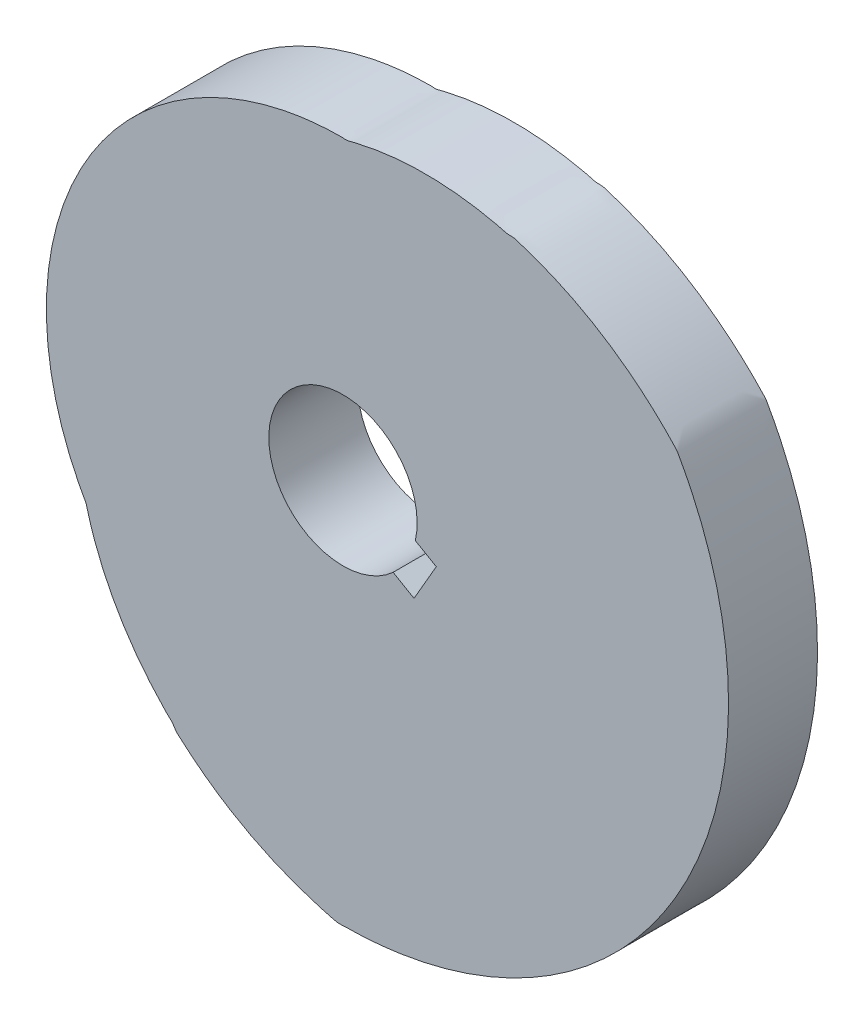
SolidWorks part; units mm, degrees
material "45"
ref_plane "前视基准面" through (0, 0, 0) normal (0, 0, 1) x (1, 0, 0)
ref_plane "上视基准面" through (0, 0, 0) normal (0, 1, 0) x (1, 0, 0)
ref_plane "右视基准面" through (0, 0, 0) normal (1, 0, 0) x (0, 0, -1)
ref_axis "基准轴1" through (0, 0, -88.99) along (0, 0, 1)
sketch "草图1" plane through (0, 0, 0) normal (0, 0, 1) x (1, 0, 0)
  arc A0 (45.0333, 26) -> (0, -52) centre (0, 0) cw construction
  arc A1 (-34.641, -20) -> (0, 40) centre (0, 0) cw construction
  spline S0 degree 3 poles (0, 40) (0.4897, 39.8817) (1.1754, 40.1373) (2.1153, 40.3446) (2.8327, 40.5043) (3.5567, 40.647) (4.2864, 40.7779) (5.0218, 40.8954) (5.7626, 40.9996) (6.5085, 41.0903) (7.2594, 41.1674) (8.0149, 41.2308) (8.7749, 41.2803) (9.539, 41.3157) (10.307, 41.337) (11.0786, 41.344) (11.8536, 41.3366) (12.6317, 41.3147) (13.4126, 41.2782) (14.1961, 41.227) (14.9818, 41.1609) (15.7696, 41.0799) (16.559, 40.9838) (17.3499, 40.8727) (18.142, 40.7465) (18.9348, 40.6045) (19.7285, 40.4491) (20.5213, 40.2713) (21.3184, 40.1047) (22.1217, 39.814) (22.9906, 39.9115) (23.7938, 39.5861) (24.5909, 39.3561) (25.3819, 39.0829) (26.1722, 38.8013) (26.9601, 38.5021) (27.7455, 38.1876) (28.5281, 37.8573) (29.3076, 37.5112) (30.0837, 37.1495) (30.856, 36.772) (31.6243, 36.3788) (32.3882, 35.97) (33.1474, 35.5455) (33.9017, 35.1055) (34.6506, 34.6499) (35.3939, 34.1788) (36.1313, 33.6923) (36.8625, 33.1905) (37.5871, 32.6733) (38.3048, 32.1409) (39.0153, 31.5933) (39.7184, 31.0308) (40.4136, 30.4532) (41.1007, 29.8608) (41.7795, 29.2537) (42.4495, 28.6319) (43.1104, 27.9957) (43.9809, 27.1265) (44.6169, 26.4556) (45.0333, 26) knots 0 0 0 0 0.028753 0.043498 0.05831 0.07319 0.088137 0.103153 0.118236 0.133387 0.148606 0.163893 0.179247 0.19467 0.21016 0.225719 0.241345 0.25704 0.272803 0.288633 0.304532 0.320499 0.336533 0.352636 0.368808 0.385047 0.401354 0.41773 0.434174 0.450686 0.468709 0.485426 0.502212 0.519065 0.535987 0.552978 0.570036 0.587164 0.604359 0.621623 0.638956 0.656356 0.673826 0.691364 0.70897 0.726645 0.744388 0.7622 0.780081 0.79803 0.816048 0.834134 0.852289 0.870512 0.888805 0.907165 0.925595 0.944093 0.96266 1 1 1 1 construction
  spline S1 degree 3 poles (0, -52) (-0.627, -52.1198) (-1.5137, -51.8369) (-2.7005, -51.5347) (-3.5851, -51.2772) (-4.4622, -51.0083) (-5.3308, -50.7236) (-6.1908, -50.4243) (-7.0421, -50.1105) (-7.8843, -49.7825) (-8.7172, -49.4403) (-9.5405, -49.0843) (-10.3541, -48.7147) (-11.1577, -48.3317) (-11.9512, -47.9355) (-12.7342, -47.5265) (-13.5066, -47.1047) (-14.2681, -46.6706) (-15.0186, -46.2242) (-15.758, -45.766) (-16.4859, -45.296) (-17.2022, -44.8147) (-17.9068, -44.3222) (-18.5995, -43.8188) (-19.2799, -43.3048) (-19.9486, -42.7807) (-20.6033, -42.2452) (-21.2512, -41.7048) (-21.865, -41.1368) (-22.5636, -40.613) (-22.9339, -39.8138) (-23.6026, -39.2718) (-24.1619, -38.6706) (-24.7286, -38.079) (-25.2764, -37.4748) (-25.8122, -36.8644) (-26.334, -36.2464) (-26.8422, -35.6216) (-27.3366, -34.9901) (-27.8173, -34.3522) (-28.284, -33.7083) (-28.7368, -33.0586) (-29.1755, -32.4034) (-29.6002, -31.743) (-30.0107, -31.0777) (-30.4071, -30.4078) (-30.7893, -29.7335) (-31.1573, -29.0552) (-31.511, -28.3732) (-31.8504, -27.6877) (-32.1755, -26.9991) (-32.4864, -26.3076) (-32.783, -25.6135) (-33.0653, -24.917) (-33.3333, -24.2186) (-33.587, -23.5185) (-33.8266, -22.8169) (-34.0519, -22.1141) (-34.3328, -21.178) (-34.5232, -20.4719) (-34.641, -20) knots 0 0 0 0 0.036854 0.055414 0.073905 0.092328 0.110683 0.128969 0.147187 0.165337 0.183418 0.201431 0.219376 0.237252 0.25506 0.272799 0.290471 0.308074 0.325609 0.343076 0.360474 0.377804 0.395066 0.41226 0.429386 0.446444 0.463433 0.480355 0.497208 0.513993 0.532068 0.54865 0.565163 0.581608 0.597985 0.614294 0.630536 0.646709 0.662815 0.678852 0.694822 0.710724 0.726558 0.742324 0.758023 0.773654 0.789217 0.804712 0.82014 0.8355 0.850792 0.866017 0.881174 0.896264 0.911286 0.92624 0.941127 0.955946 0.970698 1 1 1 1 construction
  spline S2 degree 3 poles (45.1375, 25.8187) (67.3633, -13.0375) (44.9868, -51.8072) (0.2234, -51.9995) (0.1734, -51.9997) (0.0732, -52) (-0.0767, -52.015) (-0.1763, -52.0265) (-0.2262, -52.0306) (-0.7698, -52.0746) (-1.5853, -51.8187) (-2.7005, -51.5347) (-3.5851, -51.2772) (-4.4622, -51.0083) (-5.3308, -50.7236) (-6.1908, -50.4243) (-7.0421, -50.1105) (-7.8843, -49.7825) (-8.7172, -49.4403) (-9.5405, -49.0843) (-10.3541, -48.7147) (-11.1577, -48.3317) (-11.9512, -47.9355) (-12.7342, -47.5265) (-13.5066, -47.1047) (-14.2681, -46.6706) (-15.0186, -46.2242) (-15.758, -45.766) (-16.4859, -45.296) (-17.2022, -44.8147) (-17.9068, -44.3222) (-18.5995, -43.8188) (-19.2799, -43.3048) (-19.9486, -42.7807) (-20.6033, -42.2452) (-21.2512, -41.7048) (-21.865, -41.1368) (-22.5636, -40.613) (-22.9339, -39.8138) (-23.6026, -39.2718) (-24.1619, -38.6706) (-24.7286, -38.079) (-25.2764, -37.4748) (-25.8122, -36.8644) (-26.334, -36.2464) (-26.8422, -35.6216) (-27.3366, -34.9901) (-27.8173, -34.3522) (-28.284, -33.7083) (-28.7368, -33.0586) (-29.1755, -32.4034) (-29.6002, -31.743) (-30.0107, -31.0777) (-30.4071, -30.4078) (-30.7893, -29.7335) (-31.1573, -29.0552) (-31.511, -28.3732) (-31.8504, -27.6877) (-32.1755, -26.9991) (-32.4864, -26.3076) (-32.783, -25.6135) (-33.0653, -24.917) (-33.3333, -24.2186) (-33.587, -23.5185) (-33.8266, -22.8169) (-34.0519, -22.1141) (-34.3147, -21.2382) (-34.4904, -20.5932) (-34.5949, -20.1828) (-34.6052, -20.1424) (-34.6256, -20.0617) (-34.6735, -19.9437) (-34.7149, -19.8715) (-34.7356, -19.8353) (-51.7854, 10.0224) (-34.607, 39.8062) (-0.2247, 39.9994) (-0.1743, 39.9997) (-0.0736, 40) (0.0769, 39.9809) (0.177, 39.9681) (0.2272, 39.9643) (0.6316, 39.9334) (1.2478, 40.1533) (2.1153, 40.3446) (2.8327, 40.5043) (3.5567, 40.647) (4.2864, 40.7779) (5.0218, 40.8954) (5.7626, 40.9996) (6.5085, 41.0903) (7.2594, 41.1674) (8.0149, 41.2308) (8.7749, 41.2803) (9.539, 41.3157) (10.307, 41.337) (11.0786, 41.344) (11.8536, 41.3366) (12.6317, 41.3147) (13.4126, 41.2782) (14.1961, 41.227) (14.9818, 41.1609) (15.7696, 41.0799) (16.559, 40.9838) (17.3499, 40.8727) (18.142, 40.7465) (18.9348, 40.6045) (19.7285, 40.4491) (20.5213, 40.2713) (21.3184, 40.1047) (22.1217, 39.814) (22.9906, 39.9115) (23.7938, 39.5861) (24.5909, 39.3561) (25.3819, 39.0829) (26.1722, 38.8013) (26.9601, 38.5021) (27.7455, 38.1876) (28.5281, 37.8573) (29.3076, 37.5112) (30.0837, 37.1495) (30.856, 36.772) (31.6243, 36.3788) (32.3882, 35.97) (33.1474, 35.5455) (33.9017, 35.1055) (34.6506, 34.6499) (35.3939, 34.1788) (36.1313, 33.6923) (36.8625, 33.1905) (37.5871, 32.6733) (38.3048, 32.1409) (39.0153, 31.5933) (39.7184, 31.0308) (40.4136, 30.4532) (41.1007, 29.8608) (41.7795, 29.2537) (42.4495, 28.6319) (43.1104, 27.9957) (43.932, 27.1753) (44.5217, 26.5558) (44.8932, 26.1527) (44.9243, 26.1189) (44.9866, 26.0512) (45.0689, 25.9384) (45.1147, 25.8586) (45.1375, 25.8187) (67.3633, -13.0375) (44.9868, -51.8072) knots -0.00054 0 0 0 0.342706 0.342706 0.342706 0.343279 0.343852 0.344425 0.344425 0.344425 0.350666 0.354242 0.357805 0.361355 0.364892 0.368415 0.371925 0.375422 0.378906 0.382377 0.385834 0.389278 0.39271 0.396128 0.399533 0.402924 0.406303 0.409668 0.413021 0.41636 0.419686 0.422999 0.426298 0.429585 0.432858 0.436119 0.439366 0.4426 0.446083 0.449278 0.452459 0.455628 0.458783 0.461926 0.465055 0.468171 0.471274 0.474365 0.477442 0.480506 0.483556 0.486594 0.489619 0.492631 0.495629 0.498615 0.501587 0.504547 0.507493 0.510427 0.513347 0.516255 0.519149 0.52203 0.524899 0.527754 0.530597 0.535513 0.535513 0.535513 0.535996 0.53648 0.536963 0.536963 0.536963 0.804225 0.804225 0.804225 0.80481 0.805395 0.805979 0.805979 0.805979 0.810687 0.813549 0.816424 0.819312 0.822213 0.825127 0.828055 0.830995 0.833949 0.836916 0.839896 0.842889 0.845896 0.848915 0.851948 0.854994 0.858054 0.861126 0.864212 0.867311 0.870423 0.873548 0.876687 0.879838 0.883004 0.886182 0.889373 0.892578 0.896076 0.899321 0.902578 0.905849 0.909134 0.912431 0.915742 0.919066 0.922404 0.925754 0.929118 0.932496 0.935886 0.93929 0.942707 0.946137 0.949581 0.953038 0.956509 0.959992 0.963489 0.966999 0.970523 0.97406 0.97761 0.981174 0.984751 0.988341 0.991944 0.99838 0.99838 0.99838 0.99892 0.99946 1 1 1 1.342706 1.342706 1.342706 weights 1 0.669065 0.669065 1 1 1 1 1 1 1 1 1 1 1 1 1 1 1 1 1 1 1 1 1 1 1 1 1 1 1 1 1 1 1 1 1 1 1 1 1 1 1 1 1 1 1 1 1 1 1 1 1 1 1 1 1 1 1 1 1 1 1 1 1 1 1 1 1 1 1 1 1 1 1 0.669654 0.669654 1 1 1 1 1 1 1 1 1 1 1 1 1 1 1 1 1 1 1 1 1 1 1 1 1 1 1 1 1 1 1 1 1 1 1 1 1 1 1 1 1 1 1 1 1 1 1 1 1 1 1 1 1 1 1 1 1 1 1 1 1 1 1 1 1 1 1 1 1 1 1 0.669065 0.669065 only from (45.1375, 25.8187) to (45.1375, 25.8187)
extrude "凸台-拉伸1" add sketch "草图1" along normal blind 12
sketch "草图2" plane through (0, 0, 0) normal (0, 0, 1) x (1, 0, 0)
  line L0 (9.7614, -2.1716) -> (12.5851, -3.8019)
  line L1 (12.5851, -3.8019) -> (9.5851, -8.9981)
  line L2 (9.5851, -8.9981) -> (6.7614, -7.3678)
  arc A0 (9.7614, -2.1716) -> (6.7614, -7.3678) centre (0, 0) ccw
extrude "切除-拉伸1" cut sketch "草图2" against normal blind 12 and the other way blind 12
